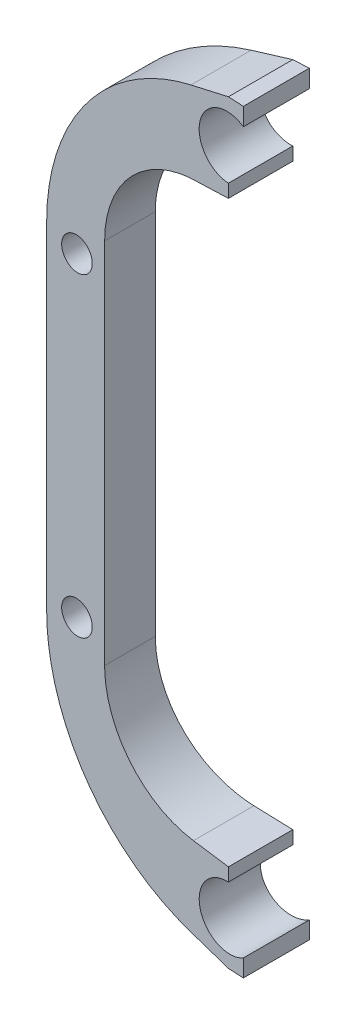
SolidWorks part; units mm, degrees
ref_plane "前视基准面" through (0, 0, 0) normal (0, 0, 1) x (1, 0, 0)
ref_plane "上视基准面" through (0, 0, 0) normal (0, 1, 0) x (1, 0, 0)
ref_plane "右视基准面" through (0, 0, 0) normal (1, 0, 0) x (0, 0, -1)
sketch "草图1" plane through (0, 0, 0) normal (0, 0, 1) x (1, 0, 0)
  line L0 (6.0175, 13.1888) -> (6.0175, -28.6712) construction
  line L1 (13.5175, 19.7888) -> (-1.4825, 19.7888) construction
  line L2 (13.5175, 19.7888) -> (13.5175, 13.7888) construction
  line L3 (13.5175, 13.7888) -> (-1.4825, 13.7888) construction
  line L10 (13.5175, 19.7888) -> (-1.4825, 13.7888) construction
  line L14 (13.5175, 13.7888) -> (-1.4825, 19.7888) construction
  line L15 (13.5175, -25.6712) -> (-1.4825, -25.6712) construction
  line L20 (13.5175, -25.6712) -> (13.5175, -31.6712) construction
  line L21 (13.5175, -31.6712) -> (-1.4825, -31.6712) construction
  line L22 (-1.4825, -25.6712) -> (-1.4825, -31.6712) construction
  line L24 (13.5175, -25.6712) -> (-1.4825, -31.6712) construction
  line L25 (13.5175, -31.6712) -> (-1.4825, -25.6712) construction
  line L26 (-1.4825, 13.7888) -> (-1.4825, 19.7888) construction
  line L27 (6.0175, 19.7888) -> (-7.0575, 16.2854)
  line L28 (-7.0575, 16.2854) -> (-7.0575, -16.1396)
  line L32 (6.0175, -25.6712) -> (-2.8875, -24.8921)
  line L34 (-2.8875, -24.8921) -> (-2.8875, 13.0097)
  line L35 (-2.8875, 13.0097) -> (6.0175, 13.7888)
  line L37 (7.0894, 18.1222) -> (7.0894, 15.0061) construction
  line L46 (6.0175, -31.6712) -> (-7.0575, -28.1677)
  line L47 (-7.0575, -28.1677) -> (-7.0575, -16.1396)
  line L48 (-4.8792, 4.7888) -> (-4.8792, -16.6712) construction
  line L49 (6.0175, 13.7888) -> (6.0175, 14.6888)
  line L51 (6.0175, 19.7888) -> (7.0894, 19.7888)
  line L52 (7.0894, 19.7888) -> (7.0894, 18.5788)
  line L53 (6.0175, -31.6712) -> (7.0894, -31.6712)
  line L54 (7.0894, -31.6712) -> (7.0894, -30.4892)
  line L55 (6.0175, -25.6712) -> (6.0175, -26.5712)
  circle A6 centre (6.0175, 16.7888) radius 2.1 construction
  circle A7 centre (6.0175, -28.6712) radius 2.1 construction
  circle A10 centre (-4.8792, 4.7888) radius 1.1
  circle A11 centre (-4.8792, -16.6712) radius 1.1
  arc A12 (7.0894, 18.5788) -> (6.0175, 14.6888) centre (6.0081, 16.7841) ccw
  arc A13 (6.0175, -26.5712) -> (7.0894, -30.4892) centre (6.0199, -28.6762) ccw
  dimension "D1" = 45.46
  dimension "D2" = 6
  dimension "D10" = 12
  dimension "D3" = 6
  dimension "D4" = 15
  dimension "D5" = 15
  dimension "D6" = 85
  dimension "D7" = 85
  dimension "D8" = 105
  dimension "D9" = 105
  dimension "D11" = 12
extrude "凸台-拉伸2" add sketch "草图1" along normal blind 4.5
fillet "圆角1" radius 7 2 edges at (-2.8875, 13.0097, 2.25) (-2.8875, -24.8921, 2.25)
fillet "圆角2" radius 14 2 edges at (-7.0575, 16.2854, 2.25) (-7.0575, -28.1677, 2.25)
fillet "圆角3" radius 2 rebuild error yes
sketch "草图2" plane through (0, 0, 0) normal (0, 1, 0) x (1, 0, 0)
  line L0 (7.0894, 0) -> (-9.9377, -0.8924) construction
  line L1 (-9.9377, -0.8924) -> (-9.6534, 2.8887)
  line L2 (-9.6534, 2.8887) -> (6.0918, 2.8887)
  line L3 (6.0918, 2.8887) -> (7.0894, 0)
  line L4 (7.0894, -4.5) -> (-9.9279, -3.6082)
  line L5 (-9.9279, -3.6082) -> (-9.6673, -5.6136)
  line L6 (-9.6673, -5.6136) -> (7.0894, -5.4075)
  line L7 (7.0894, -5.4075) -> (7.0894, -4.5)
  line L9 (-7.0575, -4.5) -> (3.319, -4.5) construction
  line L10 (3.319, 0) -> (-7.0575, 0) construction
  line L11 (7.0894, 0) -> (-4.9288, -0.6298)
  line L12 (-4.9288, -0.6298) -> (-9.5046, -0.6298)
  line L13 (-9.5046, -0.6298) -> (-9.9377, -0.8924)
  dimension "D1" = 3
  dimension "D2" = 3
extrude "切除-拉伸1" cut sketch "草图2" against normal through all both and the other way through all
